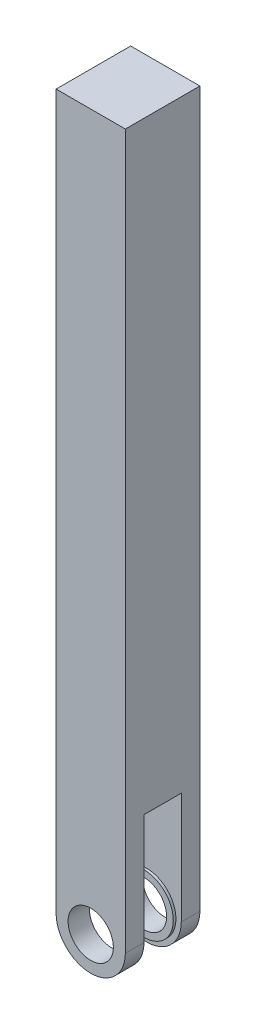
SolidWorks part; units mm, degrees
ref_plane "Front Plane" through (0, 0, 0) normal (0, 0, 1) x (1, 0, 0)
ref_plane "Top Plane" through (0, 0, 0) normal (0, 1, 0) x (1, 0, 0)
ref_plane "Right Plane" through (0, 0, 0) normal (1, 0, 0) x (0, 0, -1)
sketch "Sketch2" plane through (0, 0, 0) normal (0, 0, 1) x (1, 0, 0)
  line L1 (0, 0) -> (500, 0)
  line L2 (0, 0) -> (0, -375)
  line L3 (0, -375) -> (500, -375)
  line L4 (500, 0) -> (500, -375)
  line L5 (0, -375) -> (500, -375)
  line L6 (0, -375) -> (0, -330)
  line L7 (0, -330) -> (500, -330)
  line L8 (500, -375) -> (500, -330)
  dimension "D1" = 375
  dimension "D2" = 500
  dimension "D3" = 45
sketch "Sketch3" plane through (0, 0, 0) normal (1, 0, 0) x (0, 0, -1)
  line L1 (-91.8721, -345.9813) -> (-105.8721, -345.9813)
  line L2 (-84.8721, -369.6699) -> (-84.8721, -119.4595)
  line L3 (-84.8721, -119.4595) -> (-112.8721, -119.4595)
  line L4 (-112.8721, -369.6699) -> (-112.8721, -119.4595)
  line L6 (-84.8721, -369.6699) -> (-84.8721, -400.8824)
  line L7 (-84.8721, -400.8824) -> (-91.8721, -400.8824)
  line L8 (-91.8721, -345.9813) -> (-91.8721, -400.8824)
  line L10 (-112.8721, -369.6699) -> (-112.8721, -400.5676)
  line L11 (-112.8721, -400.5676) -> (-105.8721, -400.5676)
  line L12 (-105.8721, -345.9813) -> (-105.8721, -400.5676)
  dimension "D1" = 14
extrude "Boss-Extrude1" add sketch "Sketch3" along normal blind 26
sketch "Sketch4" plane through (0, 0, 112.8721) normal (0, 0, 1) x (1, 0, 0)
  line L0 (0, -387.8824) -> (26, -387.8824) construction
  line L1 (0, 0) -> (0, -375) construction
  line L2 (26, -119.4595) -> (26, -400.5676) construction
  line L3 (13, -400.5676) -> (13, -387.8824) construction
  line L4 (26, -400.5676) -> (0, -400.5676) construction
  line L5 (26, -400.8824) -> (0, -400.8824) construction
  circle A0 centre (13, -387.8824) radius 8.5
  dimension "D2" = 17
  dimension "D1" = 13
extrude "Cut-Extrude1" cut sketch "Sketch4" against normal blind 33
fillet "Fillet1" radius 13 4 edges at (26, -400.5676, 109.3721) (26, -400.8824, 88.3721) (0, -400.5676, 109.3721) (0, -400.8824, 88.3721)
sketch "Sketch5" plane through (0, 0, 112.8721) normal (0, 0, 1) x (1, 0, 0)
  circle A0 centre (13, -387.8824) radius 11
  circle A2 centre (13, -387.8824) radius 8.5
  dimension "D1" = 22
  dimension "D2" = 17
extrude "Boss-Extrude2" add sketch "Sketch5" against normal blind 8 contours A0 | A2
ref_plane "Plane1" through (0, 0, 98.8721) normal (0, 0, 1) x (1, 0, 0)
mirror "Mirror1" about plane through (0, 0, 98.8721) normal (0, 0, 1) of "Boss-Extrude2"
